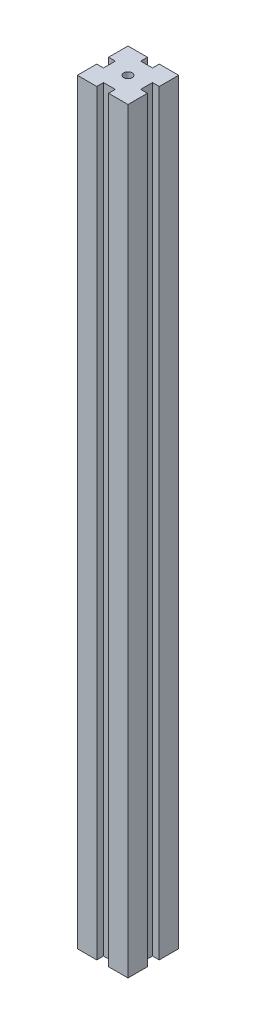
SolidWorks part; units mm, degrees
ref_plane "Front Plane" through (0, 0, 0) normal (0, 0, 1) x (1, 0, 0)
ref_plane "Top Plane" through (0, 0, 0) normal (0, 1, 0) x (1, 0, 0)
ref_plane "Right Plane" through (0, 0, 0) normal (1, 0, 0) x (0, 0, -1)
sketch "Sketch1" plane through (0, 0, 0) normal (0, 1, 0) x (1, 0, 0)
  line L0 (7.5, 15) -> (7.5, 0) construction
  line L1 (0, 0) -> (15, 0)
  line L2 (0, 0) -> (0, 15)
  line L3 (0, 15) -> (15, 15)
  line L4 (15, 0) -> (15, 15)
  line L5 (5.75, 0) -> (9.25, 0)
  line L6 (5.75, 0) -> (5.75, 2)
  line L7 (5.75, 2) -> (9.25, 2)
  line L8 (9.25, 0) -> (9.25, 2)
  line L9 (5.75, 15) -> (9.25, 15)
  line L10 (5.75, 15) -> (5.75, 13)
  line L11 (5.75, 13) -> (9.25, 13)
  line L12 (9.25, 15) -> (9.25, 13)
  line L13 (15, 9.25) -> (13, 9.25)
  line L14 (15, 9.25) -> (15, 5.75)
  line L15 (15, 5.75) -> (13, 5.75)
  line L16 (13, 9.25) -> (13, 5.75)
  line L17 (0, 9.25) -> (2, 9.25)
  line L18 (0, 9.25) -> (0, 5.75)
  line L19 (0, 5.75) -> (2, 5.75)
  line L20 (2, 9.25) -> (2, 5.75)
  line L21 (0, 7.5) -> (15, 7.5) construction
  dimension "D1" = 15
  dimension "D2" = 2
  dimension "15" = 15
  dimension "D3" = 2
  dimension "D4" = 3.5
  dimension "D5" = 3.5
extrude "Boss-Extrude1" add sketch "Sketch1" along normal blind 224 contours L17 L20 L19 L2 L1 L6 L7 L8 L4 L15 L16 L13 L3 L12 L11 L10 region at (7.5, 0, -7.5)
sketch "Sketch2" plane through (0, 224, 0) normal (0, 1, 0) x (1, 0, 0)
  line L0 (0, 15) -> (15, 0) construction
  circle A0 centre (7.5, 7.5) radius 1.25
  dimension "D1" = 2.5
extrude "Cut-Extrude1" cut sketch "Sketch2" against normal through all
